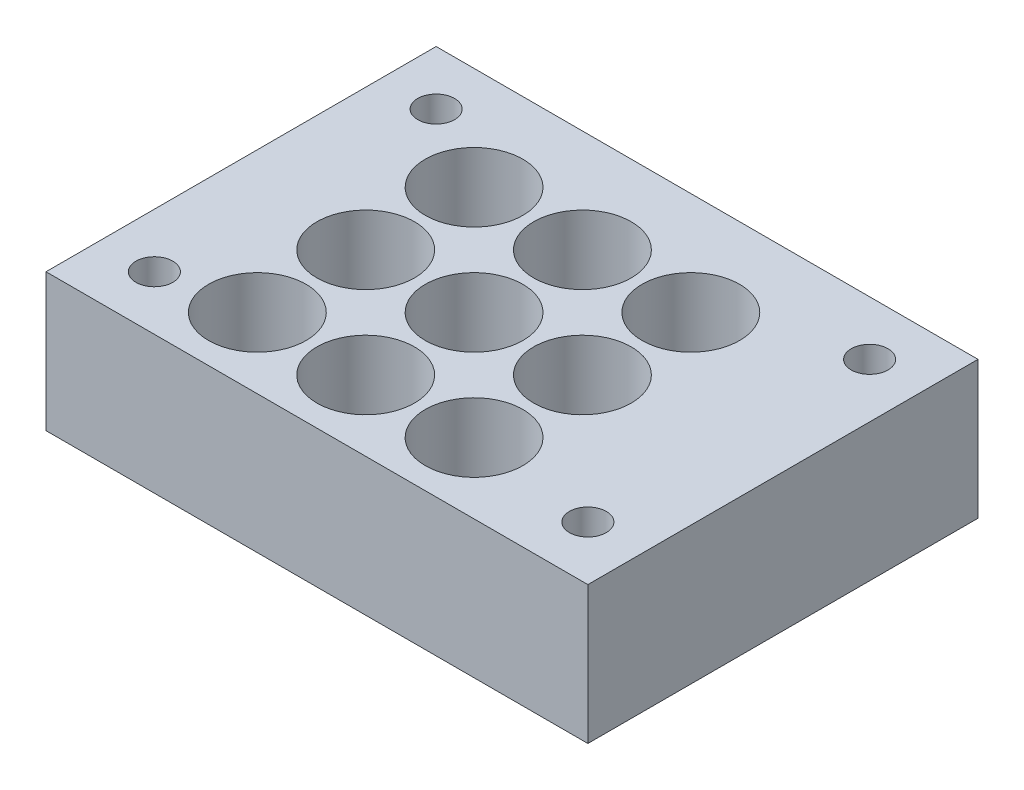
SolidWorks part; units mm, degrees
ref_plane "Front Plane" through (0, 0, 0) normal (0, 0, 1) x (1, 0, 0)
ref_plane "Top Plane" through (0, 0, 0) normal (0, 1, 0) x (1, 0, 0)
ref_plane "Right Plane" through (0, 0, 0) normal (1, 0, 0) x (0, 0, -1)
sketch "Sketch1" plane through (0, 0, 0) normal (0, 1, 0) x (1, 0, 0)
  line L0 (45, 31) -> (5, 31) construction
  line L1 (0, 0) -> (50, 0)
  line L2 (0, 0) -> (0, 36)
  line L3 (0, 36) -> (50, 36)
  line L4 (50, 0) -> (50, 36)
  line L6 (45, 31) -> (45, 5) construction
  circle A19 centre (13, 6.5) radius 4.5
  circle A28 centre (5, 5) radius 1.7
  circle A29 centre (5, 31) radius 1.7
  circle A30 centre (45, 31) radius 1.7
  circle A31 centre (45, 5) radius 1.7
  circle A32 centre (23, 6.5) radius 4.5
  circle A33 centre (33, 6.5) radius 4.5
  circle A34 centre (23, 16.5) radius 4.5
  circle A35 centre (33, 16.5) radius 4.5
  circle A36 centre (23, 26.5) radius 4.5
  circle A37 centre (33, 26.5) radius 4.5
  circle A38 centre (13, 16.5) radius 4.5
  circle A39 centre (13, 26.5) radius 4.5
  point P7 (45, 18)
  point P9 (25, 31)
  point P10 (25, 36)
  point P20 (50, 18)
  dimension "D5" = 40
  dimension "D6" = 26
  dimension "D3" = 9
  dimension "D8" = 3.4
  dimension "D1" = 50
  dimension "D2" = 36
  dimension "D4" = 8
  dimension "D7" = 1.5
  dimension "D9" = 3
extrude "Boss-Extrude1" add sketch "Sketch1" along normal blind 12.7 contours L1 L4 L3 L2 A39 A36 A34 region at (0.6161, 0, -18)
equation "\"o\"= 10mm"
equation "\"P\"= 10"
